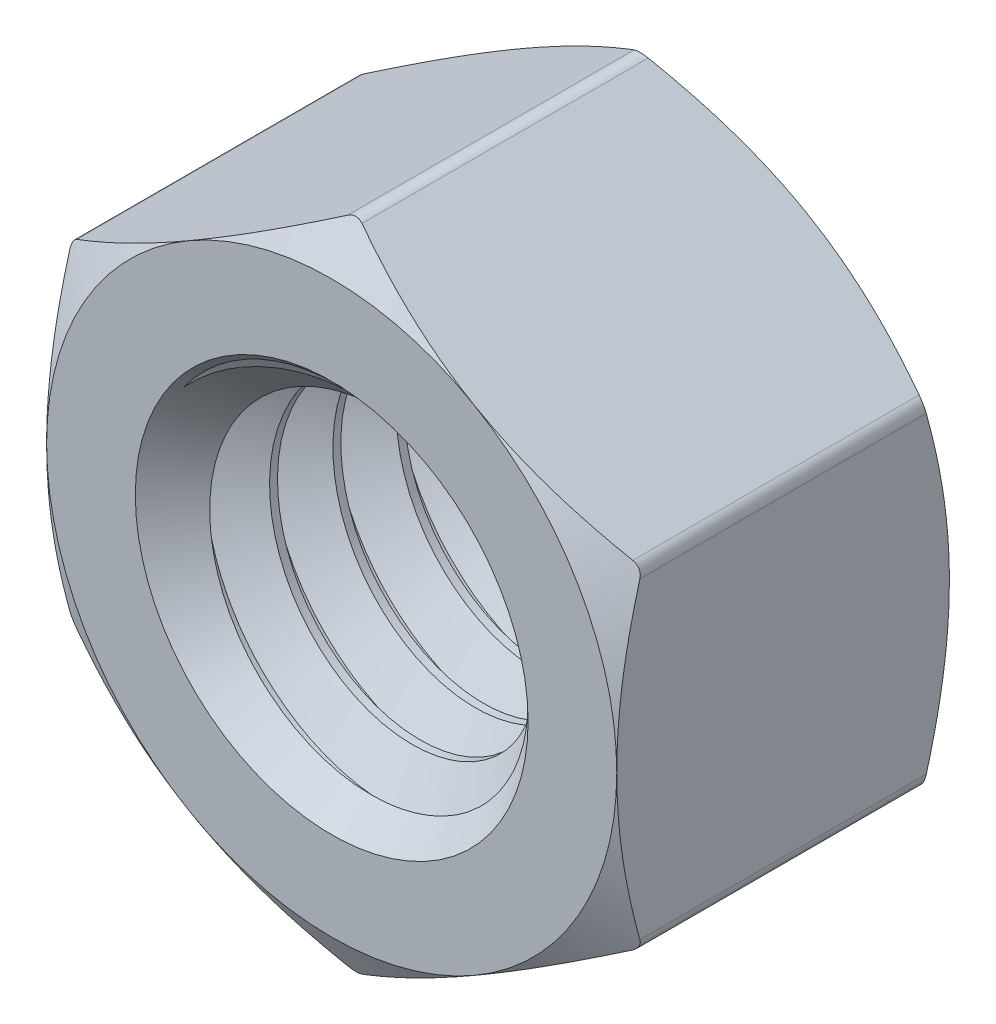
SolidWorks part; units mm, degrees
ref_plane "Front" through (0, 0, 0) normal (0, 0, 1) x (1, 0, 0)
ref_plane "Top" through (0, 0, 0) normal (0, 1, 0) x (1, 0, 0)
ref_plane "Right" through (0, 0, 0) normal (1, 0, 0) x (0, 0, -1)
sketch "Sketch1" plane through (0, 0, 0) normal (0, 0, 1) x (1, 0, 0)
  line L0 (0, 4.7625) -> (0, 3.175) construction
  line L1 (-7.1437, 4.1244) -> (-7.1437, -4.1244)
  line L2 (-7.1437, -4.1244) -> (0, -8.2489)
  line L3 (0, -8.2489) -> (7.1437, -4.1244)
  line L4 (7.1437, -4.1244) -> (7.1437, 4.1244)
  line L5 (7.1437, 4.1244) -> (0, 8.2489)
  line L6 (0, 8.2489) -> (-7.1437, 4.1244)
  circle A0 centre (0, 0) radius 7.1438 construction
  circle A1 centre (0, 0) radius 4.7625 construction
  point P10 (0, 4.7625)
  dimension "Width" = 14.2875
  dimension "Thread Size" = 9.525
  dimension "Thread Pitch" = 1.5875
sketch "Sketch2" plane through (0, 0, 0) normal (1, 0, 0) x (0, 0, -1)
  line L0 (-4.1672, 0) -> (4.1672, 0) construction
  line L1 (-4.1672, 8.2489) -> (4.1672, 8.2489) construction
  dimension "Height" = 8.3344
sketch "Sketch15" plane through (0, 0, 0) normal (0, 0, 1) x (1, 0, 0)
  line L1 (0, 8.2489) -> (-7.1437, 4.1244)
  line L2 (-7.1437, 4.1244) -> (-7.1438, -4.1244)
  line L3 (-7.1438, -4.1244) -> (0, -8.2489)
  line L4 (0, -8.2489) -> (7.1438, -4.1244)
  line L5 (7.1438, -4.1244) -> (7.1438, 4.1244)
  line L6 (7.1438, 4.1244) -> (0, 8.2489)
  circle A0 centre (0, 0) radius 7.1438 construction
extrude "Boss-Extrude2" add sketch "Sketch15" along normal mid plane 8.3344
sketch "Sketch16" plane through (0, 0, 0) normal (0, 0, 1) x (1, 0, 0)
  circle A0 centre (0, 0) radius 4.7625 construction
  circle A1 centre (0, 0) radius 4.7625
sketch "Sketch4" plane through (0, 0, -4.1672) normal (0, 0, -1) x (-1, 0, 0)
  circle A0 centre (0, 0) radius 4.7625 construction
  circle A1 centre (0, 0) radius 4.7625
extrude "Cut-Extrude4" cut sketch "Sketch16" against normal through all both and the other way through all
sketch "Sketch7" plane through (0, 0, 4.1672) normal (0, 0, 1) x (1, 0, 0)
  circle A0 centre (0, 0) radius 7.1438 construction
  circle A1 centre (0, 0) radius 7.1438
extrude "Cut-Extrude5" cut sketch "Sketch7" against normal through all draft 60 flip side to cut
mirror "Mirror4" about plane through (0, 0, 0) normal (0, 0, 1) of "Cut-Extrude5"
fillet "Fillet2" radius 0.3572 6 edges at (-7.1437, 4.1244, 0) (-7.1438, -4.1244, 0) (0, -8.2489, 0) (7.1438, -4.1244, 0) (7.1438, 4.1244, 0) (0, 8.2489, 0)
sketch "Sketch8" plane through (0, 0, 4.1672) normal (0, 0, 1) x (1, 0, 0)
  line L0 (1.2326, -4.6002) -> (0, 0) construction
  line L2 (0, 4.7625) -> (0, 3.175) construction
  circle A0 centre (0, 0) radius 4.7625 construction
  point P0 (1.2326, -4.6002)
  dimension "D1" = 15
sketch "Sketch13" plane through (0, 0, -4.1672) normal (0, 0, -1) x (-1, 0, 0)
  circle A0 centre (0, 0) radius 4.7625 construction
  circle A1 centre (0, 0) radius 4.7625
extrude "Boss-Extrude1" add sketch "Sketch13" against normal up to surface (8.3344 mm away) separate body up to face at (4.7625, 0, 4.1672)
curve "Helix/Spiral3" pitch 1.5875 height 9.9219 radius 4.7625 centre (0, 0, -4.1672) axis (0, 0, 1) start towards (0, 1, 0)
sketch "Sketch12" plane through (0, 0, 0) normal (1, 0, 0) x (0, 0, -1)
  line L0 (5.5562, 4.7625) -> (4.1672, 4.7625)
  line L1 (5.5562, 4.7625) -> (4.9609, 3.7314)
  line L2 (4.9609, 3.7314) -> (4.7625, 3.7314)
  line L3 (4.7625, 3.7314) -> (4.1672, 4.7625)
  line L4 (4.8617, 3.7314) -> (4.8617, 4.7625) construction
  line L5 (4.4648, 4.2469) -> (5.2586, 4.2469) construction
  dimension "D1" = 60
  dimension "D2" = 0.1984
  dimension "D3" = 0.7937
sweep "Cut-Sweep1" cut profiles "Sketch12" path "Helix/Spiral3" align with end faces yes
sketch "Sketch17" plane through (0, 0, 4.1672) normal (0, 0, 1) x (1, 0, 0)
  circle A1 centre (0, 0) radius 4.7625
  circle A2 centre (0, 0) radius 4.7625
  dimension "D1" = 0
extrude "Boss-Extrude3" add sketch "Sketch17" against normal up to surface (8.3344 mm away) up to face at (4.7625, 0, -4.1672)
combine bodies "Combine1" operation type subtract main body 127 bodies to subtract 118
sketch "Sketch10" plane through (0, 0, 4.1672) normal (0, 0, 1) x (1, 0, 0)
  circle A0 centre (0, 0) radius 4.7625 construction
  circle A1 centre (0, 0) radius 4.7625 construction
  circle A2 centre (0, 0) radius 4.9212
  dimension "D1" = 0.1588
extrude "Cut-Extrude2" cut sketch "Sketch10" against normal through all draft 45
sketch "Sketch11" plane through (0, 0, -4.1672) normal (0, 0, -1) x (-1, 0, 0)
  circle A1 centre (0, 0) radius 4.9212 construction
  circle A2 centre (0, 0) radius 4.9212
extrude "Cut-Extrude3" cut sketch "Sketch11" against normal through all draft 45
ref_point "Point1"
ref_point "Point2"
ref_axis "Axis1" through (0, 0, -4.1672) along (0, 0, 1)
equation "\"D1\"= \"Height@Sketch2\""
equation "\"D3@Helix/Spiral3\"=\"Height@Sketch2\"+\"Thread Pitch@Sketch1\""
equation "\"D4@Helix/Spiral3\"=\"Thread Pitch@Sketch1\""
equation "\"D2@Sketch12\" = \"D4@Helix/Spiral3\"*.125"
equation "\"D3@Sketch12\" = \"D4@Helix/Spiral3\"*.50"
equation "\"D1@Boss-Extrude2\"=\"Height@Sketch2\""
equation "\"D1@Fillet2\"=\"Width@Sketch1\"*0.025"
equation "\"D1@Sketch10\"=\"Thread Pitch@Sketch1\"*0.1"
